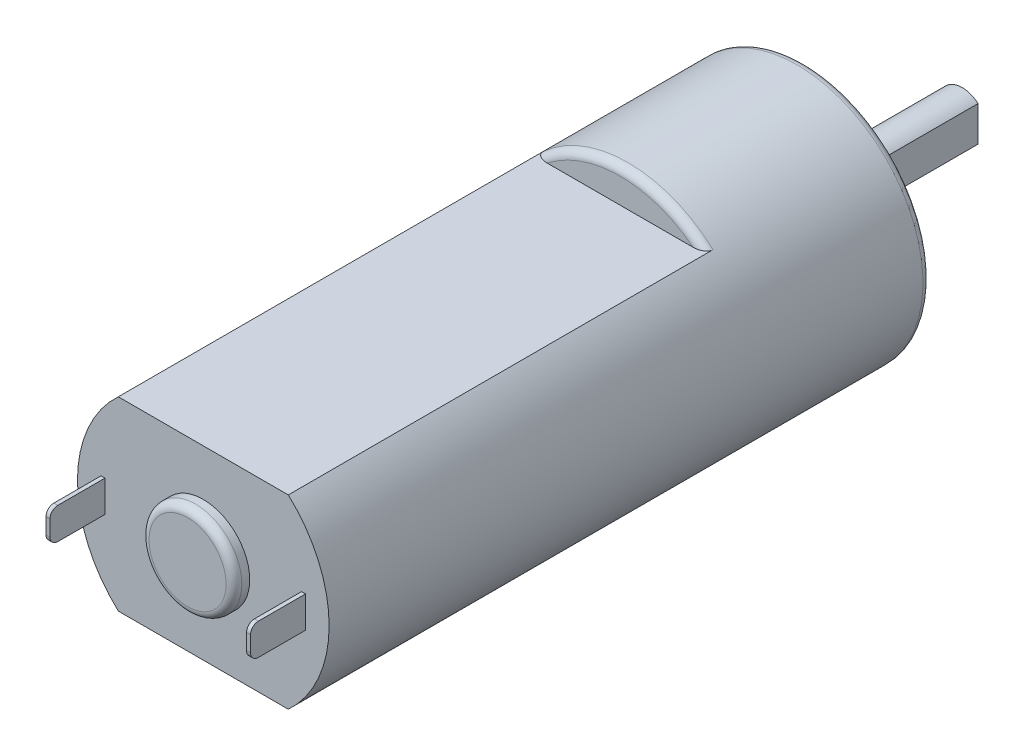
SolidWorks part; units mm, degrees
ref_plane "Front Plane" through (0, 0, 0) normal (0, 0, 1) x (1, 0, 0)
ref_plane "Top Plane" through (0, 0, 0) normal (0, 1, 0) x (1, 0, 0)
ref_plane "Right Plane" through (0, 0, 0) normal (1, 0, 0) x (0, 0, -1)
ref_plane "Plane1" through (0, 0, 0) normal (0, -1, 0) x (1, 0, 0)
sketch "Sketch1" plane through (0, 0, 0) normal (0, -1, 0) x (1, 0, 0)
  line L0 (8, 38.25) -> (0, 38.25)
  line L1 (0, 38.25) -> (0, 0)
  line L2 (0, 0) -> (8, 0)
  line L3 (8, 0) -> (8, 38.25)
  line L4 (0, 38.25) -> (0, 0) construction
revolve "Revolve1" add sketch "Sketch1" angle 360 about L4 reverse direction yes
sketch "Sketch2" plane through (0, 0, 0) normal (0, 0, -1) x (-1, 0, 0)
  circle A0 centre (0, 0) radius 3
extrude "Boss-Extrude1" add sketch "Sketch2" along normal blind 2
sketch "Sketch3" plane through (0, 0, -2) normal (0, 0, -1) x (-1, 0, 0)
  line L0 (-1, -1.118) -> (-1, 1.118)
  arc A0 (-1, 1.118) -> (-1, -1.118) centre (0, 0) cw
extrude "Boss-Extrude2" add sketch "Sketch3" along normal blind 8
sketch "Sketch4" plane through (0, 0, -2) normal (0, 0, -1) x (-1, 0, 0)
  line L0 (-1, -1.118) -> (-1, 1.118)
  arc A0 (-1, 1.118) -> (-1, -1.118) centre (0, 0) ccw
extrude "Cut-Extrude1" cut sketch "Sketch4" against normal blind 2
sketch "Sketch5" plane through (0, 0, 38.25) normal (0, 0, 1) x (1, 0, 0)
  line L0 (-5.4028, 5.9) -> (5.4028, 5.9)
  arc A0 (5.4028, 5.9) -> (-5.4028, 5.9) centre (0, 0) ccw
extrude "Cut-Extrude2" cut sketch "Sketch5" against normal blind 26.5
sketch "Sketch6" plane through (0, 0, 38.25) normal (0, 0, 1) x (1, 0, 0)
  line L0 (5.4028, -5.9) -> (-5.4028, -5.9)
  arc A0 (-5.4028, -5.9) -> (5.4028, -5.9) centre (0, 0) ccw
extrude "Cut-Extrude3" cut sketch "Sketch6" against normal blind 26.5
sketch "Sketch7" plane through (0, 0, 38.25) normal (0, 0, 1) x (1, 0, 0)
  line L0 (-6.5, 1) -> (-6.25, 1)
  line L1 (-6.25, 1) -> (-6.25, -1)
  line L2 (-6.25, -1) -> (-6.5, -1)
  line L3 (-6.5, -1) -> (-6.5, 1)
extrude "Boss-Extrude3" add sketch "Sketch7" along normal blind 3.5
sketch "Sketch8" plane through (0, 0, 38.25) normal (0, 0, 1) x (1, 0, 0)
  line L0 (6.25, 1) -> (6.5, 1)
  line L1 (6.5, 1) -> (6.5, -1)
  line L2 (6.5, -1) -> (6.25, -1)
  line L3 (6.25, -1) -> (6.25, 1)
extrude "Boss-Extrude4" add sketch "Sketch8" along normal blind 3.5
sketch "Sketch9" plane through (0, 0, 38.25) normal (0, 0, 1) x (1, 0, 0)
  circle A0 centre (0, 0) radius 2.95
extrude "Boss-Extrude5" add sketch "Sketch9" along normal blind 1
fillet "Fillet1" radius 0.5 8 edges at (-6.375, 1, 41.75) (6.375, 1, 41.75) (6.375, -1, 41.75) (0, -8, 11.75) (-6.375, -1, 41.75) (0, 8, 11.75) (-8, 0, 0) (2.95, 0, 39.25) tangent propagation no
